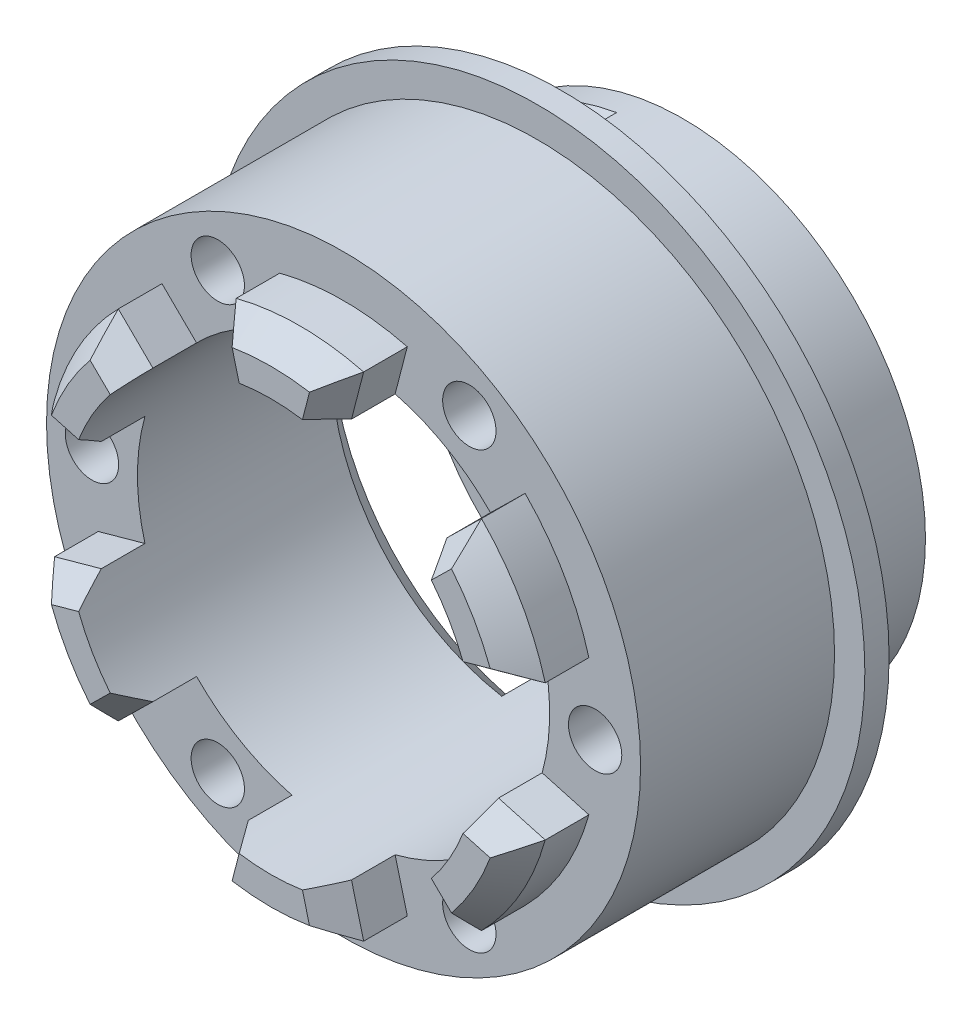
SolidWorks part; units mm, degrees
ref_plane "정면" through (0, 0, 0) normal (0, 0, 1) x (1, 0, 0)
ref_plane "윗면" through (0, 0, 0) normal (0, 1, 0) x (1, 0, 0)
ref_plane "우측면" through (0, 0, 0) normal (1, 0, 0) x (0, 0, -1)
sketch "스케치1" plane through (0, 0, 0) normal (0, 0, 1) x (1, 0, 0)
  circle A0 centre (0, 0) radius 10
  dimension "D1" = 20
extrude "보스-돌출1" add sketch "스케치1" along normal blind 2
sketch "스케치2" plane through (0, 0, 2) normal (0, 0, 1) x (1, 0, 0)
  circle A0 centre (0, 0) radius 10
  circle A1 centre (0, 0) radius 8.5
  circle A5 centre (0, 0) radius 10 construction
  dimension "D1" = 1.5
extrude "보스-돌출2" add sketch "스케치2" along normal blind 3
sketch "스케치4" plane through (0, 0, 5) normal (0, 0, 1) x (1, 0, 0)
  circle A0 centre (0, 0) radius 13.5
  circle A1 centre (0, 0) radius 8.5
  circle A2 centre (0, 0) radius 8.5 construction
  dimension "D1" = 27
extrude "보스-돌출3" add sketch "스케치4" along normal blind 1
sketch "스케치5" plane through (0, 0, 6) normal (0, 0, 1) x (1, 0, 0)
  circle A0 centre (0, 0) radius 8.5
  circle A1 centre (0, 0) radius 12.25
  circle A2 centre (0, 0) radius 8.5 construction
  dimension "D1" = 24.5
extrude "보스-돌출4" add sketch "스케치5" along normal blind 8
sketch "스케치6" plane through (0, 0, 14) normal (0, 0, 1) x (1, 0, 0)
  circle A0 centre (0, 0) radius 10.375 construction
  circle A6 centre (0, 0) radius 8.5 construction
  circle A8 centre (10.375, 0) radius 1.1
  circle A9 centre (5.1875, -8.985) radius 1.1
  circle A10 centre (-5.1875, -8.985) radius 1.1
  circle A11 centre (-10.375, 0) radius 1.1
  circle A12 centre (-5.1875, 8.985) radius 1.1
  circle A13 centre (5.1875, 8.985) radius 1.1
  point P19 (0, 0)
  point P20 (0, 0)
  dimension "D1" = 1.875
  dimension "D2" = 2.2
  dimension "D3" = 6
extrude "컷-돌출1" cut sketch "스케치6" against normal blind 8
sketch "스케치7" plane through (0, 0, 0) normal (0, 0, -1) x (-1, 0, 0)
  circle A0 centre (0, 0) radius 7 construction
  circle A5 centre (0, 0) radius 3
  circle A6 centre (-7, 0) radius 1.15
  circle A7 centre (7, 0) radius 1.15
  circle A9 centre (0, 7) radius 1.15
  circle A11 centre (0, -7) radius 1.15
  dimension "D1" = 14
  dimension "D2" = 2.3
  dimension "D4" = 6
extrude "컷-돌출2" cut sketch "스케치7" against normal through all
sketch "스케치10" plane through (0, 0, 14) normal (0, 0, 1) x (1, 0, 0)
  line L0 (-2.1282, 8.2293) -> (-2.629, 10.1656)
  line L2 (6.0626, 5.9577) -> (7.4891, 7.3595)
  line L4 (-8.1909, 2.2715) -> (-10.1181, 2.806)
  line L6 (8.1909, -2.2715) -> (10.1181, -2.806)
  line L8 (2.1282, -8.2293) -> (2.629, -10.1656)
  line L10 (-6.0626, -5.9577) -> (-7.4891, -7.3595)
  line L12 (-6.0626, 5.9577) -> (-7.4891, 7.3595)
  line L14 (2.1282, 8.2293) -> (2.629, 10.1656)
  line L16 (8.1909, 2.2715) -> (10.1181, 2.806)
  line L18 (6.0626, -5.9577) -> (7.4891, -7.3595)
  line L20 (-2.1282, -8.2293) -> (-2.629, -10.1656)
  line L22 (-8.1909, -2.2715) -> (-10.1181, -2.806)
  arc A0 (-7.4891, 7.3595) -> (-10.1181, 2.806) centre (0, 0) ccw
  arc A1 (-8.1909, -2.2715) -> (-6.0626, -5.9577) centre (0, 0) ccw
  arc A2 (2.629, 10.1656) -> (-2.629, 10.1656) centre (0, 0) ccw
  arc A3 (10.1181, 2.806) -> (7.4891, 7.3595) centre (0, 0) ccw
  arc A4 (7.4891, -7.3595) -> (10.1181, -2.806) centre (0, 0) ccw
  arc A5 (-2.629, -10.1656) -> (2.629, -10.1656) centre (0, 0) ccw
  arc A6 (-10.1181, -2.806) -> (-7.4891, -7.3595) centre (0, 0) ccw
  arc A7 (-2.1282, -8.2293) -> (2.1282, -8.2293) centre (0, 0) ccw
  arc A8 (6.0626, -5.9577) -> (8.1909, -2.2715) centre (0, 0) ccw
  arc A9 (8.1909, 2.2715) -> (6.0626, 5.9577) centre (0, 0) ccw
  arc A10 (2.1282, 8.2293) -> (-2.1282, 8.2293) centre (0, 0) ccw
  arc A11 (-6.0626, 5.9577) -> (-8.1909, 2.2715) centre (0, 0) ccw
  circle A12 centre (0, 0) radius 8.5 construction
  circle A13 centre (0, 0) radius 8.5 construction
  point P30 (0, 0)
  point P48 (0, 0)
  point P61 (0, 0)
  dimension "D1" = 2
extrude "보스-돌출5" add sketch "스케치10" along normal blind 3
chamfer "모따기1" distance 1.2 angle 35 18 edges at (-9.0933, -5.25, 17) (0, -10.5, 17) (9.0933, -5.25, 17) (9.0933, 5.25, 17) (0, 10.5, 17) (-9.0933, 5.25, 17) (-9.1545, -2.5388, 17) (-6.7759, -6.6586, 17) (2.3786, -9.1974, 17) (-2.3786, -9.1974, 17) (6.7759, -6.6586, 17) (9.1545, -2.5388, 17) (9.1545, 2.5388, 17) (6.7759, 6.6586, 17) (2.3786, 9.1974, 17) (-2.3786, 9.1974, 17) (-9.1545, 2.5388, 17) (-6.7759, 6.6586, 17) first distance on face at (-8.9484, -5.1664, 15.5) first distance on face at (0, -10.3328, 15.5) first distance on face at (8.9484, -5.1664, 15.5) first distance on face at (8.9484, 5.1664, 15.5) first distance on face at (0, 10.3328, 15.5) first distance on face at (-8.9484, 5.1664, 15.5) first distance on face at (-9.1545, -2.5388, 15.5) first distance on face at (-6.7759, -6.6586, 15.5) first distance on face at (2.3786, -9.1974, 15.5) first distance on face at (-2.3786, -9.1974, 15.5) first distance on face at (6.7759, -6.6586, 15.5) first distance on face at (9.1545, -2.5388, 15.5) first distance on face at (9.1545, 2.5388, 15.5) first distance on face at (6.7759, 6.6586, 15.5) first distance on face at (2.3786, 9.1974, 15.5) first distance on face at (-2.3786, 9.1974, 15.5) first distance on face at (-9.1545, 2.5388, 15.5) first distance on face at (-6.7759, 6.6586, 15.5)
sketch "스케치11" plane through (0, 0, 0) normal (0, 0, -1) x (-1, 0, 0)
  line L0 (0, 0) -> (1.7365, 9.8481)
  line L1 (0, 0) -> (1.7365, -9.8481)
  line L2 (0, 0) -> (10, 0) construction
  circle A0 centre (0, 0) radius 10
  circle M6 centre (7, 0) radius 1.15
  circle M9 centre (0, 0) radius 3
  circle M10 centre (0, 0) radius 10
  dimension "D1" = 80
  dimension "D2" = 80
extrude "컷-돌출3" cut sketch "스케치11" against normal blind 3 from offset 2 contours L2 A0 L0 M9 M6 | L2 L1 M9 M10 M6 region at (-4.961, 4.3448, 0) region at (-4.961, -4.3448, 0) offset against normal yes
chamfer "모따기2" distance 1 angle 45 2 edges at (-8.5, 0, 5) (-10, 0, 2)
